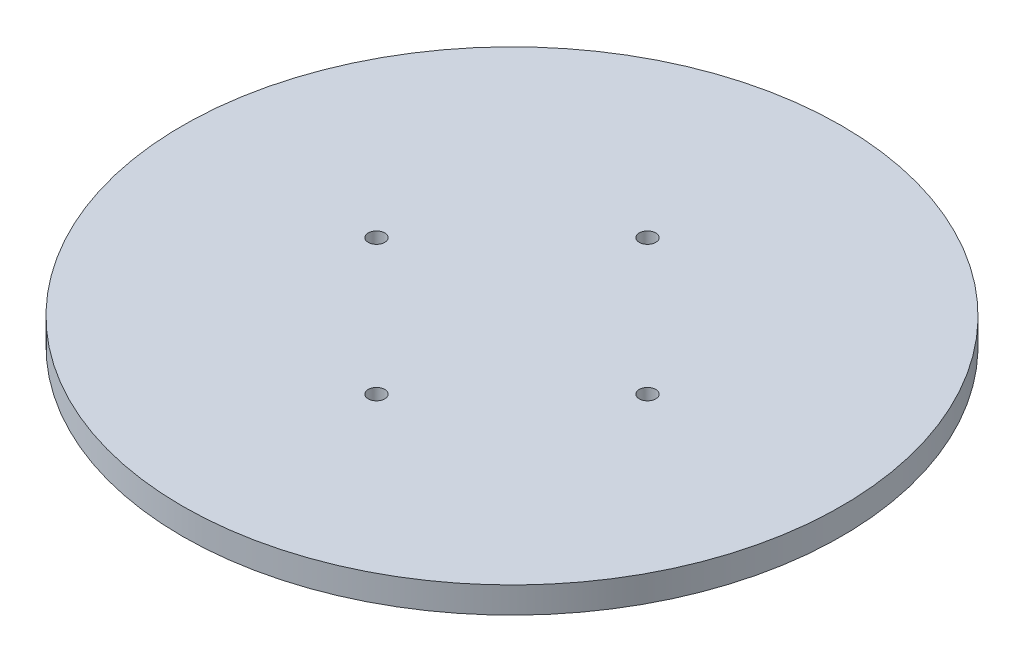
SolidWorks part; units mm, degrees
ref_plane "Front Plane" through (0, 0, 0) normal (0, 0, 1) x (1, 0, 0)
ref_plane "Top Plane" through (0, 0, 0) normal (0, 1, 0) x (1, 0, 0)
ref_plane "Right Plane" through (0, 0, 0) normal (1, 0, 0) x (0, 0, -1)
sketch "Sketch1" plane through (0, 0, 0) normal (0, 1, 0) x (1, 0, 0)
  line L5 (-40, -40) -> (40, 40) construction
  line L6 (-40, 40) -> (40, -40) construction
  circle A0 centre (0, 0) radius 40
  point P0 (0, 0)
  dimension "D3" = 80
  dimension "D1" = 80
  dimension "D2" = 80
extrude "Boss-Extrude1" add sketch "Sketch1" along normal mid plane 3.175
sketch "Sketch2" plane through (0, -1.5875, 0) normal (0, -1, 0) x (1, 0, 0)
  circle A0 centre (-16.45, 0) radius 0.85 construction
  circle A1 centre (0, -16.45) radius 0.85 construction
  circle A2 centre (0, 16.45) radius 0.85 construction
  circle A3 centre (16.45, 0) radius 0.85 construction
  circle A4 centre (-16.45, 0) radius 0.85
  circle A5 centre (0, -16.45) radius 0.85
  circle A6 centre (0, 16.45) radius 0.85
  circle A7 centre (16.45, 0) radius 0.85
  circle A8 centre (0, -16.45) radius 1
  circle A9 centre (16.45, 0) radius 1
  circle A10 centre (0, 16.45) radius 1
  circle A11 centre (-16.45, 0) radius 1
  dimension "D1" = 2
extrude "Cut-Extrude2" cut sketch "Sketch2" against normal through all contours A7 | A9 A7 | A8 A5 | A5 | A11 A4 | A4 | A10 A6 | A6 region at (-16.45, -1.5875, 0) region at (0, -1.5875, -16.45) region at (0, -1.5875, 16.45) region at (16.45, -1.5875, 0) region at (-0.9717, -1.5875, -16.45) region at (15.4783, -1.5875, 0) region at (-0.9717, -1.5875, 16.45) region at (-17.4217, -1.5875, 0)
